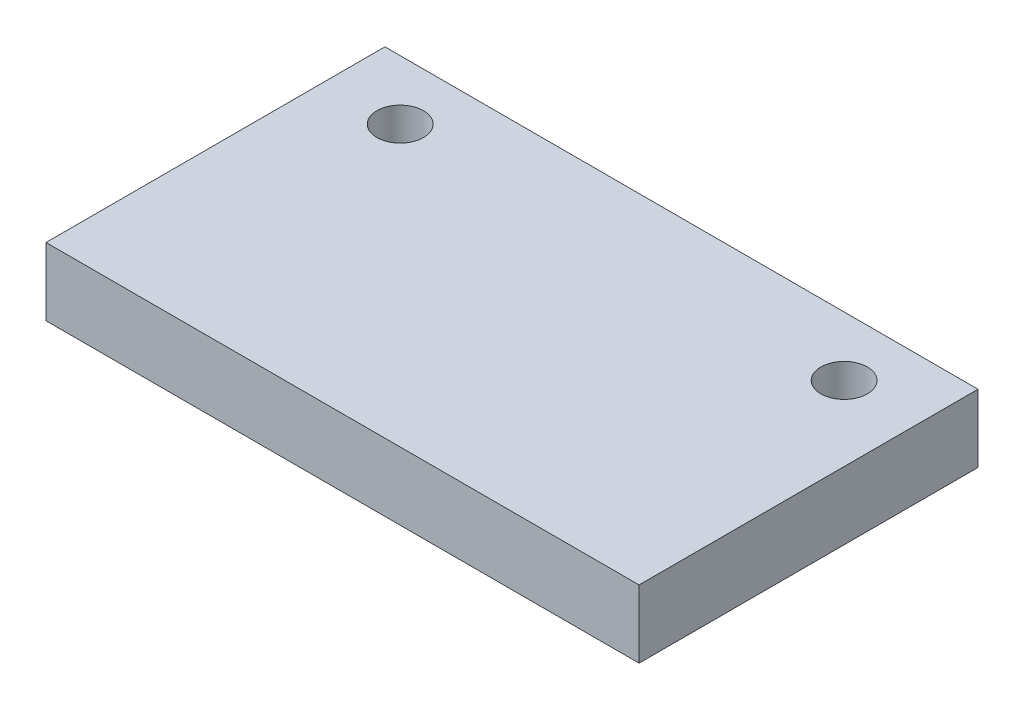
SolidWorks part; units mm, degrees
ref_plane "Front Plane" through (0, 0, 0) normal (0, 0, 1) x (1, 0, 0)
ref_plane "Top Plane" through (0, 0, 0) normal (0, 1, 0) x (1, 0, 0)
ref_plane "Right Plane" through (0, 0, 0) normal (1, 0, 0) x (0, 0, -1)
sketch "Sketch1" plane through (0, 0, 0) normal (0, 1, 0) x (1, 0, 0)
  line L1 (-321.608, 142.4623) -> (378.392, 142.4623)
  line L2 (-321.608, 142.4623) -> (-321.608, -257.5377)
  line L3 (-321.608, -257.5377) -> (378.392, -257.5377)
  line L4 (378.392, 142.4623) -> (378.392, -257.5377)
  dimension "D1" = 700
  dimension "D2" = 400
extrude "Boss-Extrude1" add sketch "Sketch1" along normal blind 80
sketch "Sketch3" plane through (0, 80, 0) normal (0, 1, 0) x (1, 0, 0)
  line L0 (28.392, 142.4623) -> (28.392, -257.5377) construction
  line L4 (-321.608, -257.5377) -> (378.392, -257.5377) construction
  line L5 (-321.608, -57.5377) -> (378.392, -57.5377) construction
  line L6 (-321.608, 142.4623) -> (-321.608, -257.5377) construction
  line L7 (378.392, -257.5377) -> (378.392, 142.4623) construction
  line L8 (-321.608, 142.4623) -> (28.392, 142.4623) construction
  circle A0 centre (-233.5765, 72.4748) radius 27.5
  circle A1 centre (290.3604, 72.4748) radius 27.5
extrude "Cut-Extrude1" cut sketch "Sketch3" against normal blind 80 contours A0
extrude "Cut-Extrude2" cut sketch "Sketch3<4>" against normal blind 80 contours A1
sketch "Sketch3<4>" plane through (0, 80, 0) normal (0, 1, 0) x (1, 0, 0) same geometry as "Sketch3"
